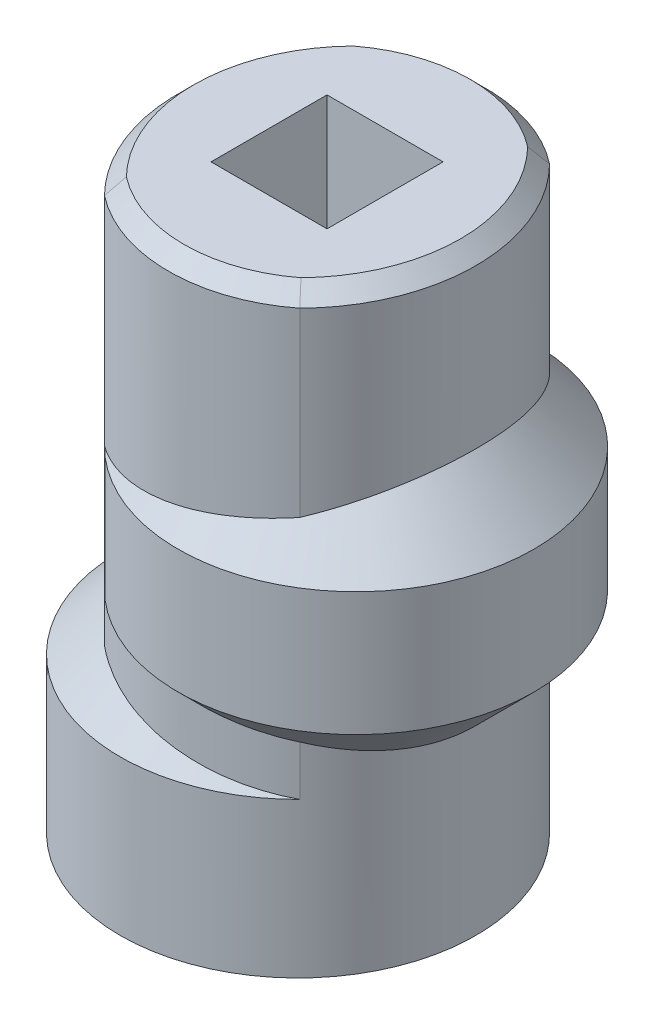
SolidWorks part; units mm, degrees
material "ABS"
ref_plane "Front Plane" through (0, 0, 0) normal (0, 0, 1) x (1, 0, 0)
ref_plane "Top Plane" through (0, 0, 0) normal (0, 1, 0) x (1, 0, 0)
ref_plane "Right Plane" through (0, 0, 0) normal (1, 0, 0) x (0, 0, -1)
sketch "Sketch1" plane through (0, 0, 0) normal (0, 1, 0) x (1, 0, 0)
  line L0 (0.75, 0) -> (0, 0) construction
  line L1 (0, 0) -> (-0.75, 0) construction
  arc A0 (-2.525, -3.2302) -> (2.525, -3.2302) centre (0, 0) ccw
  arc A1 (-2.525, 3.2302) -> (-2.525, -3.2302) centre (0.75, 0) ccw
  arc A2 (2.525, 3.2302) -> (2.525, -3.2302) centre (-0.75, 0) cw
  arc A3 (2.525, 3.2302) -> (-2.525, 3.2302) centre (0, 0) ccw
  dimension "D1" = 8.2
  dimension "D3" = 4.6
  dimension "D5" = 4.6
  dimension "D2" = 0.75
  dimension "D4" = 0.75
extrude "Boss-Extrude1" add sketch "Sketch1" along normal blind 15.4
sketch "Sketch2" plane through (0, 0, 0) normal (0, 0, 1) x (1, 0, 0)
  line L0 (3.85, 0) -> (3.85, 4)
  line L1 (2.35, 5.5) -> (-0.75, 5.5)
  line L2 (-0.75, 5.5) -> (-0.75, 0)
  line L3 (-0.75, 0) -> (3.85, 0)
  line L4 (-2.525, 0) -> (2.525, 0) construction
  line L5 (3.85, 4) -> (2.35, 5.5)
  line L7 (2.35, 2.75) -> (-3.85, 2.75) construction
  line L8 (-3.85, 15.4) -> (-3.85, 0) construction
  point P0 (3.85, 0)
  point P1 (3.85, 5.5)
  point P16 (-0.75, 2.75)
  dimension "D1" = 0.75
  dimension "D2" = 5.5
  dimension "D3" = 4.6
revolve "Revolve1" add sketch "Sketch2" angle 360 about L2
sketch "Sketch3" plane through (0, 0, 0) normal (0, 0, 1) x (1, 0, 0)
  line L0 (-5.35, 0) -> (3.85, 0) construction
  line L1 (0.75, 4.7) -> (-2.35, 4.7)
  line L2 (0.75, 4.7) -> (0.75, 10.9)
  line L3 (0.75, 10.9) -> (-2.35, 10.9)
  line L4 (-3.85, 6.2) -> (-3.85, 9.4)
  line L6 (-2.35, 10.9) -> (-3.85, 9.4)
  line L7 (-2.35, 4.7) -> (-3.85, 6.2)
  point P1 (-3.85, 10.9)
  point P3 (-3.85, 4.7)
  dimension "D1" = 0.75
  dimension "D2" = 6.2
  dimension "D3" = 4.6
  dimension "D4" = 4.7
revolve "Revolve2" add sketch "Sketch3" angle 360 about L2
sketch "Sketch4" plane through (0, 0, 0) normal (0, -1, 0) x (1, 0, 0)
  line L1 (0, 2.5) -> (0, -1.9) construction
  line L3 (-2, -1.9) -> (2, -1.9) construction
  line L4 (-2, -2) -> (2, -2)
  arc A0 (2.2136, -1.1618) -> (-2.2136, -1.1618) centre (0, 0) ccw construction
  arc A2 (-2, -1.9) -> (-2.2136, -1.1618) centre (-2, -1.5) cw construction
  arc A3 (2, -1.9) -> (2.2136, -1.1618) centre (2, -1.5) ccw construction
  arc A4 (2, -2) -> (2.34, -1.1334) centre (2, -1.5) ccw
  arc A5 (2.34, -1.1334) -> (-2.34, -1.1334) centre (0, 0) ccw
  arc A6 (-2, -2) -> (-2.34, -1.1334) centre (-2, -1.5) cw
  point P14 (0, -1.9)
  dimension "D1" = 2.5
  dimension "D3" = 0.4
  dimension "D4" = 0.1
  dimension "D2" = 4.4
extrude "Cut-Extrude1" cut sketch "Sketch4" against normal offset from surface (9.4 mm away) 6 up to face at (0, 15.4, 0)
sketch "Sketch5" plane through (0, 15.4, 0) normal (0, 1, 0) x (1, 0, 0)
  line L0 (-1.5, 1.5) -> (1.5, -1.5) construction
  line L1 (-1.5, 1.5) -> (1.5, 1.5)
  line L2 (-1.5, 1.5) -> (-1.5, -1.5)
  line L3 (-1.5, -1.5) -> (1.5, -1.5)
  line L4 (1.5, 1.5) -> (1.5, -1.5)
  point P5 (0, 0)
  point P7 (0, 0)
  dimension "D1" = 3
  dimension "D2" = 3
extrude "Cut-Extrude2" cut sketch "Sketch5" against normal up to next
chamfer "Chamfer1" distance 0.4 angle 45 4 edges at (0, 15.4, -4.1) (-3.85, 15.4, 0) (0, 15.4, 4.1) (3.85, 15.4, 0)
